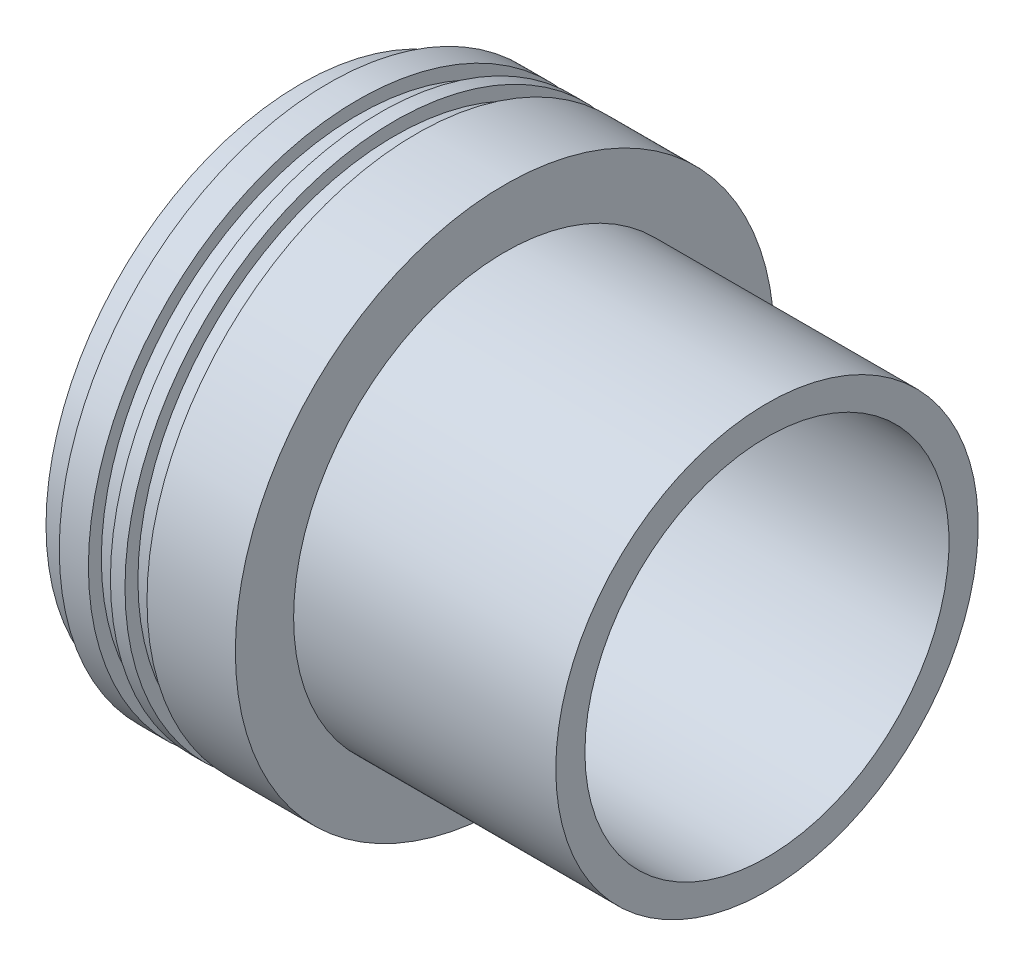
SolidWorks part; units mm, degrees
material "Epoxy, Unfilled"
ref_plane "Front Plane" through (0, 0, 0) normal (0, 0, 1) x (1, 0, 0)
ref_plane "Top Plane" through (0, 0, 0) normal (0, 1, 0) x (1, 0, 0)
ref_plane "Right Plane" through (0, 0, 0) normal (1, 0, 0) x (0, 0, -1)
sketch "Sketch1" plane through (0, 0, 0) normal (0, 0, 1) x (1, 0, 0)
  line L0 (0, 0) -> (0, 9.525)
  line L2 (0, 9.525) -> (25.4, 9.525)
  line L4 (25.4, 9.525) -> (34.925, 19.05)
  line L5 (44.45, 0) -> (44.45, 12.7)
  line L6 (34.925, 19.05) -> (101.6, 19.05)
  line L9 (44.45, 12.7) -> (101.6, 12.7)
  line L10 (101.6, 12.7) -> (101.6, 19.05)
  line L12 (0, 58.7375) -> (98.3752, 58.7375) construction
  line L17 (6.0659, 0) -> (12.4159, 0)
  line L18 (6.0659, 0) -> (6.0659, 3.175)
  line L19 (6.0659, 3.175) -> (0, 3.175)
  line L20 (12.4159, 0) -> (12.4159, 2.8194)
  line L21 (12.4159, 2.8194) -> (17.2165, 2.8194)
  line L22 (17.2165, 2.8194) -> (17.2165, 0)
  line L23 (17.2165, 0) -> (20.3915, 0)
  line L24 (20.3915, 0) -> (20.3915, 2.8194)
  line L25 (20.3915, 2.8194) -> (25.1921, 2.8194)
  line L26 (25.1921, 2.8194) -> (25.1921, 0)
  line L27 (25.1921, 0) -> (44.45, 0)
  dimension "D1" = 57.15
  dimension "D2" = 25.4
  dimension "D3" = 58.7375
  dimension "D4" = 9.525
  dimension "D5" = 9.525
  dimension "D6" = 6.35
  dimension "D7" = 66.675
  dimension "D8" = 44.45
  dimension "D9" = 12.7
  dimension "D10" = 4.8006
  dimension "D11" = 4.8006
  dimension "D12" = 3.175
  dimension "D13" = 2.8194
  dimension "D14" = 2.8194
revolve "Revolve1" add sketch "Sketch1" angle 360 about L12 region at (1.0337, 6.35, 0)
